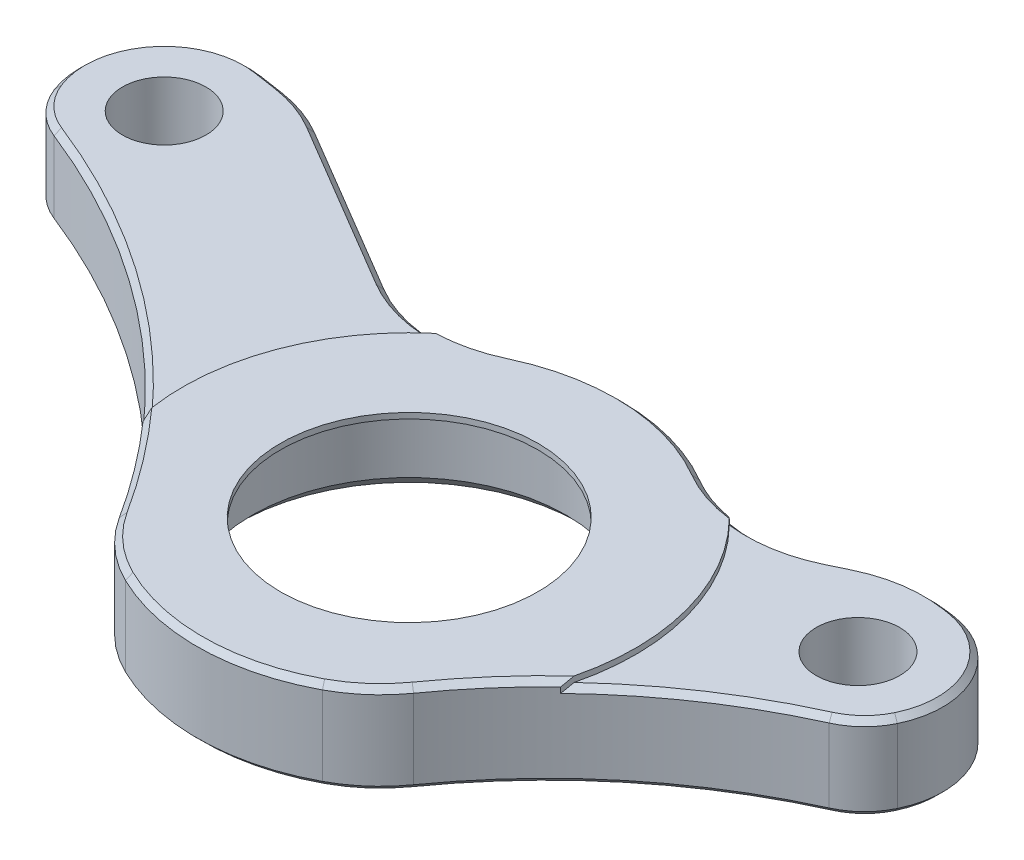
SolidWorks part; units mm, degrees
ref_plane "Front Plane" through (0, 0, 0) normal (0, 0, 1) x (1, 0, 0)
ref_plane "Top Plane" through (0, 0, 0) normal (0, 1, 0) x (1, 0, 0)
ref_plane "Right Plane" through (0, 0, 0) normal (1, 0, 0) x (0, 0, -1)
sketch "Sketch1" plane through (0, 0, 0) normal (0, 1, 0) x (1, 0, 0)
  line L0 (-9.6218, -11.5074) -> (-37.9445, 12.1742)
  line L1 (-33.2001, 22.71) -> (24.5619, 13.9894)
  line L2 (27.5149, 3.4537) -> (9.6218, -11.5074)
  line L3 (-34.0958, 16.7772) -> (0, 0) construction
  line L4 (0, 0) -> (23.6662, 8.0567) construction
  line L5 (23.6662, 8.0567) -> (-34.0958, 16.7772) construction
  circle A0 centre (0, 0) radius 11.1
  arc A1 (-9.6218, -11.5074) -> (9.6218, -11.5074) centre (0, 0) ccw
  arc A2 (24.5619, 13.9894) -> (27.5149, 3.4537) centre (23.6662, 8.0567) cw
  arc A3 (-37.9445, 12.1742) -> (-33.2001, 22.71) centre (-34.0958, 16.7772) cw
  circle A4 centre (-34.0958, 16.7772) radius 2.95
  circle A5 centre (23.6662, 8.0567) radius 2.95
  dimension "D1" = 22.2
  dimension "D2" = 15
  dimension "D3" = 6
  dimension "D4" = 38
  dimension "D6" = 5.9
  dimension "D8" = 5.9
  dimension "D5" = 135
  dimension "D7" = 25
extrude "Boss-Extrude1" add sketch "Sketch1" along normal blind 6.4
sketch "Sketch6" plane through (0, 6.4, 0) normal (0, 1, 0) x (1, 0, 0)
  line L0 (-10.3975, 10.8116) -> (-29.543, 22.1578)
  line L1 (24.5619, 13.9894) -> (-33.2001, 22.71) construction
  line L2 (11.3133, 9.8493) -> (21.0661, 14.5172)
  line L3 (-29.543, 22.1578) -> (21.0661, 14.5172)
  line L4 (-32.5918, 19.315) -> (-12.4369, 7.3705) construction
  line L5 (-12.4369, 7.3705) -> (-10.3975, 10.8116) construction
  line L6 (-12.4369, 7.3705) -> (0, 0) construction
  line L7 (22.3927, 10.7176) -> (0, 0) construction
  line L8 (11.3133, 9.8493) -> (13.0402, 6.2413) construction
  arc A1 (-10.3975, 10.8116) -> (11.3133, 9.8493) centre (0, 0) cw
  circle A2 centre (-34.0958, 16.7772) radius 2.95 construction
  circle A3 centre (23.6662, 8.0567) radius 2.95 construction
  dimension "D1" = 15
  dimension "D2" = 4
  dimension "D3" = 4
extrude "Cut-Extrude4" cut sketch "Sketch6" against normal up to next
chamfer "Chamfer1" distance 1 angle 45 1 edges at (0, 6.4, 11.1)
sketch "Sketch5" plane through (0, 6.4, 0) normal (0, 1, 0) x (1, 0, 0)
  line L1 (-37.9445, 12.1742) -> (-9.6218, -11.5074) construction
  line L2 (-37.9445, 12.1742) -> (-9.6218, -11.5074)
  line L4 (9.6218, -11.5074) -> (27.5149, 3.4537) construction
  line L5 (9.6218, -11.5074) -> (27.5149, 3.4537)
  arc A0 (-37.9445, 12.1742) -> (-9.6218, -11.5074) centre (-57.0167, -39.4131) cw
  arc A1 (27.5149, 3.4537) -> (9.6218, -11.5074) centre (43.1118, -33.3803) ccw
  dimension "D1" = 55
  dimension "D2" = 40
extrude "Cut-Extrude3" cut sketch "Sketch5" against normal through all
fillet "Fillet1" radius 10 6 edges at (9.6218, 3.2, 11.5074) (-9.6218, 3.2, 11.5074) (21.0661, 3.2, -14.5172) (11.3133, 3.2, -9.8493) (-10.3975, 3.2, -10.8116) (-29.543, 3.2, -22.1578)
fillet "Fillet2" radius 5 2 edges at (27.5149, 3.2, -3.4537) (-37.9445, 3.2, -12.1742)
sketch "Sketch7" plane through (0, 0, 0) normal (0, -1, 0) x (1, 0, 0)
  circle A0 centre (0, 0) radius 11.1 construction
  circle A1 centre (0, 0) radius 11.1
  circle A4 centre (0, 0) radius 9.1
  circle A5 centre (0, 0) radius 9.1
  dimension "D1" = 2
extrude "Boss-Extrude2" add sketch "Sketch7" against normal blind 0.4
sketch "Sketch9" plane through (0, 0, 0) normal (0, -1, 0) x (1, 0, 0)
  circle A0 centre (0, 0) radius 16
  dimension "D1" = 32
extrude "Cut-Extrude5" cut sketch "Sketch9" against normal blind 0.4 flip side to cut
sketch "Sketch10" plane through (0, 0.4, 0) normal (0, -1, 0) x (1, 0, 0)
  line L2 (-33.2001, -22.71) -> (-31.471, -22.4489)
  line L3 (-27.8655, -21.1637) -> (-15.779, -14.0008)
  line L4 (-33.2001, -22.71) -> (-31.471, -22.4489)
  line L5 (-27.8655, -21.1637) -> (-15.779, -14.0008)
  arc A6 (-9.8074, -12.6418) -> (-15.779, -14.0008) centre (-10.6807, -22.6036) ccw
  arc A7 (-15.6934, 3.1173) -> (-9.8074, -12.6418) centre (0, 0) ccw
  arc A8 (-36.8592, -11.7599) -> (-15.6934, 3.1173) centre (-57.0167, 39.4131) ccw
  arc A9 (-36.8592, -11.7599) -> (-39.6814, -14.586) centre (-35.0268, -16.412) ccw
  arc A10 (-39.6814, -14.586) -> (-33.2001, -22.71) centre (-34.0958, -16.7772) ccw
  arc A11 (-31.471, -22.4489) -> (-27.8655, -21.1637) centre (-32.9638, -12.561) ccw
  arc A12 (-9.8074, -12.6418) -> (-15.779, -14.0008) centre (-10.6807, -22.6036) ccw
  arc A13 (-15.6934, 3.1173) -> (-9.8074, -12.6418) centre (0, 0) ccw
  arc A14 (-36.8592, -11.7599) -> (-15.6934, 3.1173) centre (-57.0167, 39.4131) ccw
  arc A15 (-36.8592, -11.7599) -> (-39.6814, -14.586) centre (-35.0268, -16.412) ccw
  arc A16 (-39.6814, -14.586) -> (-33.2001, -22.71) centre (-34.0958, -16.7772) ccw
  arc A17 (-31.471, -22.4489) -> (-27.8655, -21.1637) centre (-32.9638, -12.561) ccw
  dimension "D1" = 0
extrude "Cut-Extrude6" cut sketch "Sketch10" against normal blind 0.15
chamfer "Chamfer2" distance 0.4 angle 45 40 edges at (9.1813, 0, -12.1867) (0.6642, 0, -14.9853) (-8.0671, 0, -12.9512) (12.7875, 0, 7.2951) (8.9736, 0, 11.9094) (0.2843, 0, 14.9973) (-8.8535, 0, 11.9526) (-13.0309, 0, 6.3941) (-8.8535, 6.4, 11.9526) (0.2843, 6.4, 14.9973) (-22.0306, 6.4, -3.0248) (8.9736, 6.4, 11.9094) (-38.5647, 6.4, -12.8789) (17.6887, 6.4, 2.4987) (-38.7861, 6.4, -20.5191) (28.0543, 6.4, -4.0382) (-32.3356, 6.4, -22.5795) (28.9749, 6.4, -10.8527) (-29.6062, 6.4, -21.9804) (24.3332, 6.4, -14.024) (-21.8223, 6.4, -17.5823) (21.1343, 6.4, -14.0608) (-11.1483, 6.4, -12.6145) (17.6251, 6.4, -12.8703) (0.6642, 6.4, -14.9853) (12.2207, 6.4, -11.5788) (13.9863, 0.4, -11.6612) (17.6251, 0.4, -12.8703) (21.1343, 0.4, -14.0608) (20.6438, 0.4, 0.2866) (28.0543, 0.4, -4.0382) (28.9749, 0.4, -10.8527) (24.3332, 0.4, -14.024) (-25.3891, 0.55, -5.5835) (-38.5647, 0.55, -12.8789) (-38.7861, 0.55, -20.5191) (-32.3356, 0.55, -22.5795) (-29.6062, 0.55, -21.9804) (-12.8998, 0.55, -12.8529) (-21.8223, 0.55, -17.5823)
mirror "Mirror1" about plane through (0, 0, 0) normal (0, 1, 0) of bodies 113 106
delete or keep bodies "Body-Delete/Keep 1" type delete bodies bodies 113
